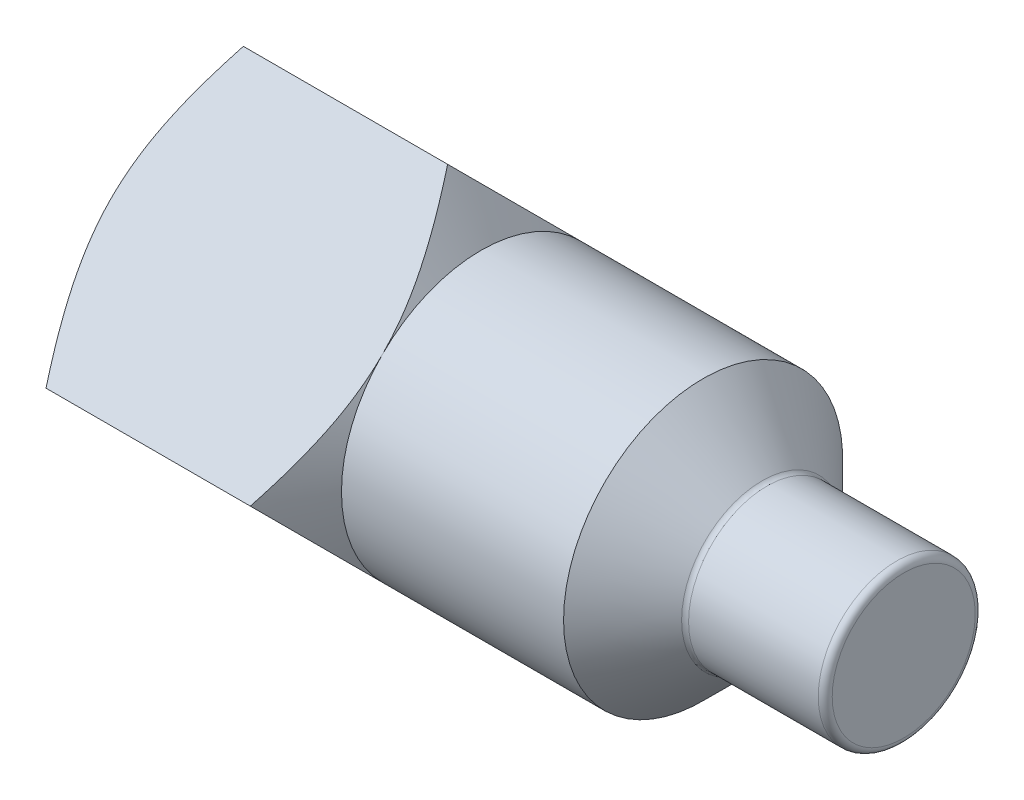
SolidWorks part; units mm, degrees
ref_plane "Front Plane" through (0, 0, 0) normal (0, 0, 1) x (1, 0, 0)
ref_plane "Top Plane" through (0, 0, 0) normal (0, 1, 0) x (1, 0, 0)
ref_plane "Right Plane" through (0, 0, 0) normal (1, 0, 0) x (0, 0, -1)
sketch "BaseHeadSke" plane through (0, 0, 0) normal (1, 0, 0) x (0, 0, -1)
  line L0 (0, 0) -> (14.1701, 0) construction
  line L1 (0, 0) -> (0, 11.9761) construction
  line L2 (0, 2.8284) -> (2.8284, 0)
  line L3 (0, -2.8284) -> (2.8284, 0)
  line L4 (0, 2.8284) -> (-2.8284, 0)
  line L5 (0, -2.8284) -> (-2.8284, 0)
  dimension "Width_flats" = 4
  dimension "Angle" = 45
extrude "BaseHead" add sketch "BaseHeadSke" along normal blind 4
sketch "HeadChamferSke" plane through (0, 0, 0) normal (0, 0, 1) x (1, 0, 0)
  line L0 (0, 0) -> (6.1973, 0) construction
  line L1 (2, 2.8284) -> (2, -3.5627) construction
  line L2 (4, 2.8284) -> (0, 2.8284) construction
  line L3 (0, 2.8284) -> (0, 1.9)
  line L4 (0, 2.8284) -> (0.536, 2.8284)
  line L5 (0.536, 2.8284) -> (0, 1.9)
  line L6 (0, 2.8284) -> (0, 0) construction
  line L7 (3.464, 2.8284) -> (4, 1.9)
  line L8 (4, 2.8284) -> (3.464, 2.8284)
  line L9 (4, 2.8284) -> (4, 1.9)
  dimension "Head_chamfer" = 3.8
  dimension "Angle" = 30
revolve "HeadChamfer" cut sketch "HeadChamferSke" angle 360 about L0
sketch "BodySke" plane through (0, 0, 0) normal (0, 0, 1) x (1, 0, 0)
  line L0 (0, 0) -> (13.1857, 0) construction
  line L1 (4, -1.9) -> (4, 1.9) construction
  line L2 (4, 0) -> (4, 1.9) construction
  line L3 (3.464, 2) -> (10, 2) construction
  line L4 (10, 2) -> (10, 0) construction
  line L5 (4, 1.9) -> (4, 2) construction
  line L6 (3.464, 2) -> (3.464, 0)
  line L7 (3.464, 0) -> (10, 0)
  line L8 (8, 2) -> (8, 1.125)
  line L9 (8, 1.125) -> (10, 1.125)
  line L10 (3.464, 2) -> (8, 2)
  line L11 (10, 1.125) -> (10, 0)
  line L12 (9.3, 2.4466) -> (9.3, -2.0631) construction
  point P14 (3.464, 1.61)
  dimension "Minor_dia" = 3.22
  dimension "Advance" = 0.7
revolve "BaseBody" add sketch "BodySke" angle 360 about L0
cosmetic thread "ThreadCosmetic" [suppressed] parameters "Minor_dia"=3.22
sketch "ChamferEndSke" plane through (0, 0, 0) normal (0, 0, 1) x (1, 0, 0)
  line L0 (0, 0) -> (11.0843, 0) construction
  line L1 (8, 2) -> (8, 1.125)
  line L2 (8, 2) -> (7.125, 2)
  line L3 (7.125, 2) -> (8, 1.125)
  line L4 (8, 2) -> (3.9423, 2) construction
  dimension "Angle" = 45
revolve "ChamferEnd" cut sketch "ChamferEndSke" angle 360 about L0
sketch "ThdSchSke" plane through (0, 0, 0) normal (0, 0, 1) x (1, 0, 0)
  line L0 (6.425, 2.4503) -> (6.425, 2)
  line L1 (6.425, 2.4503) -> (6.8753, 2.4503)
  line L2 (6.8753, 2.4503) -> (6.8753, 2)
  line L3 (6.8753, 2) -> (6.6502, 1.61)
  line L4 (6.6502, 1.61) -> (6.425, 2)
  line L5 (0, 0) -> (11.8711, 0) construction
  line L9 (7.125, 2) -> (3.9423, 2) construction
  dimension "D1" = 0.7
revolve "ThreadSchematic" [suppressed] cut sketch "ThdSchSke" angle 360 about L5
pattern_linear "ThdSchPat" [suppressed] count 3 of bodies 105
fillet "Fillet1" radius 0.1 2 edges at (10, 0, 1.125) (8, 0, 1.125)
equation "\"Minor_dia@ThreadCosmetic\" = \"Minor_dia@BodySke\""
equation "\"D1@ThdSchSke\" = \"Advance@BodySke\""
equation "\"Advance@ThdSchPat\" = \"Advance@BodySke\""
equation "\"D1@ThdSchPat\" =  int( (  \"Length@BodySke\" -  \"Length_Dog@BodySke\" )  /\"Advance@ThdSchPat\" )  - 2"
